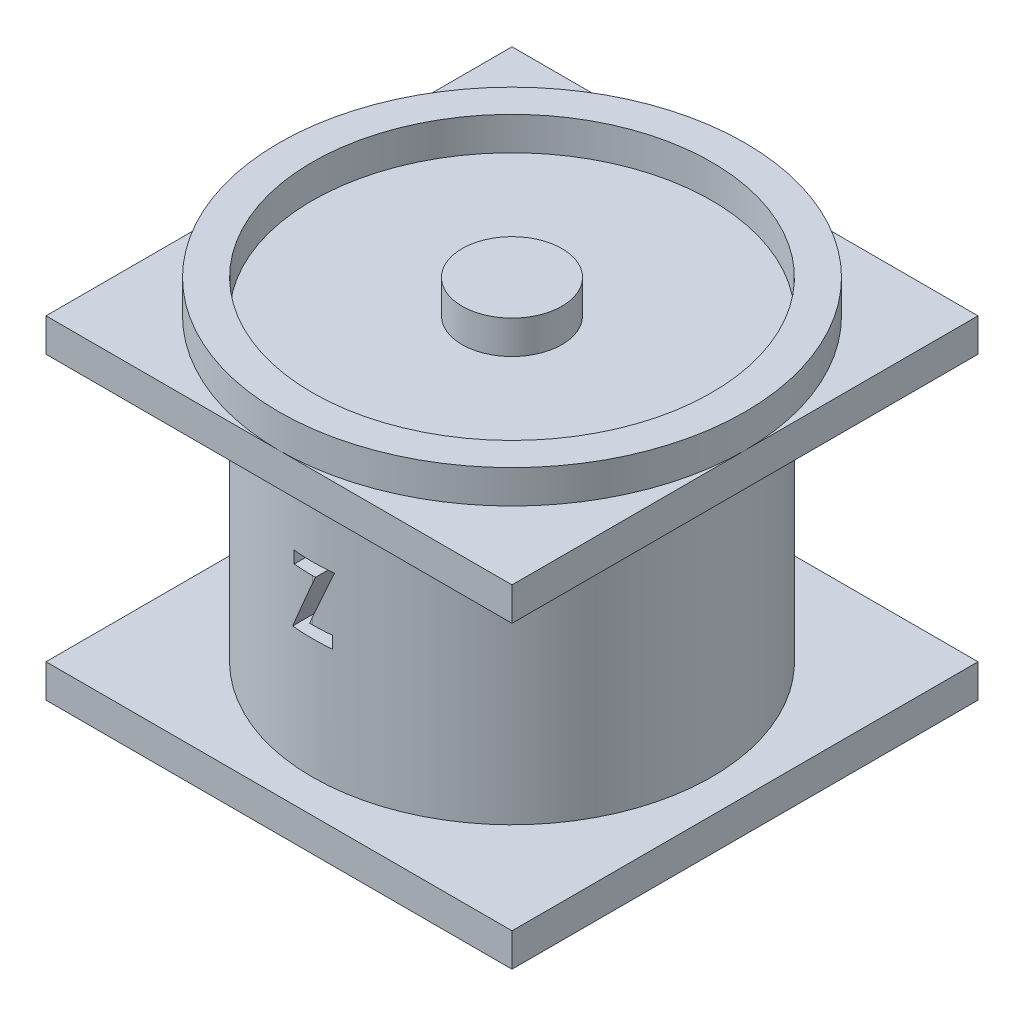
SolidWorks part; units mm, degrees
ref_plane "Front Plane" through (0, 0, 0) normal (0, 0, 1) x (1, 0, 0)
ref_plane "Top Plane" through (0, 0, 0) normal (0, 1, 0) x (1, 0, 0)
ref_plane "Right Plane" through (0, 0, 0) normal (1, 0, 0) x (0, 0, -1)
sketch "Sketch1" plane through (0, 0, 0) normal (0, 1, 0) x (1, 0, 0)
  line L1 (-70, 70) -> (70, 70)
  line L2 (-70, 70) -> (-70, -70)
  line L3 (-70, -70) -> (70, -70)
  line L4 (70, 70) -> (70, -70)
  line L5 (-70, 70) -> (70, -70) construction
  line L6 (-70, -70) -> (70, 70) construction
  point P0 (0, 0)
  dimension "D1" = 140
  dimension "D2" = 140
extrude "Boss-Extrude1" add sketch "Sketch1" along normal blind 10
sketch "Sketch2" plane through (0, 10, 0) normal (0, 1, 0) x (1, 0, 0)
  circle A0 centre (0, 0) radius 60
  dimension "D1" = 120
extrude "Boss-Extrude2" add sketch "Sketch2" along normal blind 80
sketch "Sketch3" plane through (0, 90, 0) normal (0, 1, 0) x (1, 0, 0)
  line L1 (-70, 70) -> (70, 70)
  line L2 (-70, 70) -> (-70, -70)
  line L3 (-70, -70) -> (70, -70)
  line L4 (70, 70) -> (70, -70)
  line L5 (-70, 70) -> (70, -70) construction
  line L6 (-70, -70) -> (70, 70) construction
  point P0 (0, 0)
extrude "Boss-Extrude3" add sketch "Sketch3" along normal blind 10
sketch "Sketch4" plane through (0, 100, 0) normal (0, 1, 0) x (1, 0, 0)
  circle A0 centre (0, 0) radius 70
  circle A1 centre (0, 0) radius 60
  dimension "D1" = 120
  dimension "D2" = 140
extrude "Boss-Extrude4" add sketch "Sketch4" along normal blind 10
sketch "Sketch5" plane through (0, 100, 0) normal (0, 1, 0) x (1, 0, 0)
  circle A0 centre (0, 0) radius 15
extrude "Boss-Extrude5" add sketch "Sketch5" along normal mid plane 20 separate body
ref_plane "Plane6" through (0, 0, 60) normal (0, 0, 1) x (1, 0, 0)
sketch "Sketch6" plane through (0, 0, 60) normal (0, 0, 1) x (1, 0, 0)
  text T0 "Z" font "Century Gothic" height 20
extrude "Cut-Extrude1" cut sketch "Sketch6" against normal blind 10
sketch "Sketch7" plane through (0, 0, 0) normal (0, -1, 0) x (1, 0, 0)
  circle A0 centre (0, 0) radius 40
  dimension "D1" = 80
extrude "Cut-Extrude3" cut sketch "Sketch7" against normal blind 80
